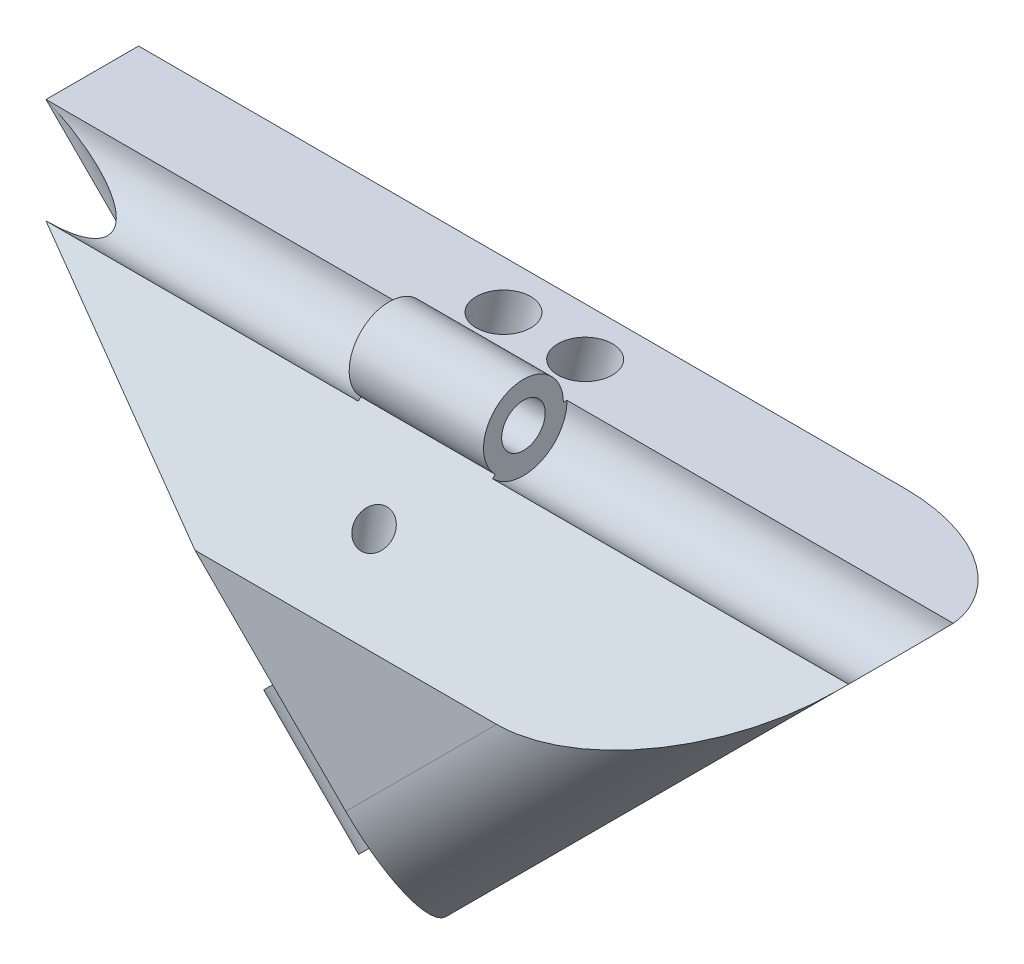
SolidWorks part; units mm, degrees
ref_plane "Front Plane" through (0, 0, 0) normal (1, 0, 0) x (0, 1, 0)
ref_plane "Top Plane" through (0, 0, 0) normal (0, 0, 1) x (0, 1, 0)
ref_plane "Right Plane" through (0, 0, 0) normal (0, 1, 0) x (-1, 0, 0)
sketch "Sketch1" plane through (0, 0, 0) normal (0, 0, 1) x (0, 1, 0)
  line L9 (8.3333, 25) -> (8.3333, -25)
  line L10 (-16.6667, 0) -> (8.3333, -25)
  line L11 (-16.6667, 0) -> (8.3333, 25)
  line L12 (-4.1667, 12.5) -> (8.3333, -25) construction
  line L13 (8.3333, 25) -> (-4.1667, -12.5) construction
  point P1 (0, 0)
  dimension "D1" = 50
  dimension "D2" = 90
extrude "Boss-Extrude1" add sketch "Sketch1" along normal blind 15
sketch "Sketch2" plane through (0, 0, 0) normal (1, 0, 0) x (0, 1, 0)
  line L0 (0.8333, 15) -> (8.3333, 7.5)
  line L1 (8.3333, 15) -> (8.3333, 0) construction
  line L2 (8.3333, 7.5) -> (8.3333, 15)
  line L3 (8.3333, 15) -> (0.8333, 15)
  line L4 (-16.6667, 15) -> (8.3333, 15) construction
  line L5 (8.3333, 5.1) -> (8.3333, 5.3)
  circle A0 centre (8.3333, 7.5) radius 1.2
  circle A1 centre (8.3333, 7.5) radius 2.4
  circle A2 centre (8.3333, 7.5) radius 2.2
  dimension "D2" = 2.4
  dimension "D3" = 0.2
  dimension "D4" = 1
  dimension "D1" = 7.5
extrude "Cut-Extrude1" cut sketch "Sketch2" against normal through all both and the other way through all contours A1 L2 L3 L0 | A2 L2 A1 L0 | L2 A2 L0 A0 | L0 A2 L2 A0 | L0 A0 L2 | L2 A0 L0 | A1 region at (0, 5.6669, 12.8113) region at (0, 7.4751, 9.572) region at (0, 7.6811, 9.0747) region at (0, 7.0873, 8.6581) region at (0, 8.035, 8.2203) region at (0, 8.376, 7.3971)
extrude "Boss-Extrude2" add sketch "Sketch2<5>" along normal blind 3.7 and the other way blind 3.7 contours A2 L0 A1 L5 | A2 L2 A0 L0 | L2 A2 L0 A0 region at (0, 6.6734, 9.0928) region at (0, 7.6811, 9.0747) region at (0, 7.0873, 8.6581)
sketch "Sketch2<5>" plane through (0, 0, 0) normal (1, 0, 0) x (0, 1, 0) same geometry as "Sketch2"
sketch "Sketch4" plane through (8.3333, -8.3333, 0) normal (0.7071, -0.7071, 0) x (0.7071, 0.7071, 0)
  line L0 (-11.7851, 7.5) -> (-4.2851, 15)
  line L1 (-11.7851, 15) -> (-11.7851, 0) construction
  line L2 (-11.7851, 15) -> (12.9636, 15) construction
  line L3 (-4.2851, 15) -> (-11.7851, 15)
  line L4 (-11.7851, 15) -> (-11.7851, 7.5)
  line L5 (-11.7851, 5.1) -> (-11.7851, 7.5)
  circle A0 centre (-11.7851, 7.5) radius 1.2
  circle A1 centre (-11.7851, 7.5) radius 2.2
  circle A2 centre (-11.7851, 7.5) radius 2.4
  line M6 (12.9636, 15) -> (-11.7851, 15)
  line M7 (-11.7851, 15) -> (-11.7851, 0)
  dimension "D1" = 2.4
  dimension "D2" = 1
  dimension "D3" = 0.2
extrude "Cut-Extrude2" cut sketch "Sketch4" against normal through all contours L0 A0 L4 | A0 L0 M7 | L5 A1 L0 A0 | L0 A1 L4 A0 | L0 A2 L4 A1 | A2 L0 M6 M7 | A2 region at (0.211, -16.4557, 8.2203) region at (0.4098, -16.2568, 7.2599) region at (0.4612, -16.2055, 9.0747) region at (0.896, -15.7706, 6.9751) region at (0.6069, -16.0598, 9.572) region at (1.8855, -14.7812, 12.8113)
extrude "Boss-Extrude3" add sketch "Sketch4<3>" against normal blind 7.4 from offset 3.8 contours A2 L0 A1 M7 | L5 A1 L0 A0 | L4 A1 L5 A0 | L0 A1 L4 A0 region at (0.4612, -16.2055, 9.0747) region at (0.896, -15.7706, 6.9751) region at (-0.8833, -17.55, 7.5) region at (1.1737, -15.4929, 9.0928) offset against normal yes
sketch "Sketch4<3>" plane through (8.3333, -8.3333, 0) normal (0.7071, -0.7071, 0) x (0.7071, 0.7071, 0) same geometry as "Sketch4"
ref_plane "Plane1" through (0, 0, 2.65) normal (0, 0, 1) x (0, 1, 0)
fillet "Fillet1" radius 5.5 1 edges at (12.5, -4.1667, 0)
fillet "Fillet2" radius 5.5 1 edges at (11.4017, -5.265, 15)
sketch "Sketch8" plane through (-6.8183, -6.8183, 9.6426) normal (-0.5, -0.5, 0.7071) x (0.866, -0.2887, 0.4082)
  line L0 (3.0196, -3.1517) -> (7.8731, 3.7122) construction
  line L1 (-0.0015, -1.0155) -> (6.0406, -5.2879) construction
  line L2 (-0.0867, 9.3407) -> (9.5061, 2.5575) construction
  circle A0 centre (5.4463, 0.2803) radius 1
  dimension "D1" = 2
sketch "Sketch10" plane through (0, 7.9167, 7.9167) normal (0, 0.7071, 0.7071) x (-1, 0, 0)
  line L0 (0, 1.6107) -> (0, 10.0173) construction
  line L1 (3.7, 1.6107) -> (-3.7, 1.6107) construction
  line L2 (-9.7218, 10.0173) -> (6.8934, 10.0173) construction
  circle A0 centre (0, 5.814) radius 1
  dimension "D1" = 2
loft "Cut-Loft1" cut profiles "Sketch10", "Sketch8" connector at (-0.78, 4.248, 11.5854) connector at (-2.943, -7.6876, 11.7682)
sketch "Sketch11" plane through (-8.3333, -8.3333, 0) normal (-0.7071, -0.7071, 0) x (0.7071, -0.7071, 0)
  line L0 (3.5351, 2.65) -> (5.0351, 2.65) construction
  line L1 (4.2851, 5.3) -> (4.2851, 0) construction
  line L2 (0.5851, 5.3) -> (7.9851, 5.3) construction
  line L3 (-23.5702, 0) -> (6.2851, 0) construction
  circle A0 centre (2.0351, 2.65) radius 1.5
  circle A1 centre (6.5351, 2.65) radius 1.5
  point P4 (3.5351, 2.65)
  point P5 (5.0351, 2.65)
  point P14 (4.2851, 2.65)
  dimension "D1" = 3
  dimension "D2" = 1.5
sketch "Sketch12" plane through (0, 8.3333, 0) normal (0, 1, 0) x (-1, 0, 0)
  line L0 (0, 5.3) -> (0, 0) construction
  line L1 (3.7, 5.3) -> (-3.7, 5.3) construction
  line L2 (-0.75, 2.65) -> (0.75, 2.65) construction
  circle A0 centre (-2.25, 2.65) radius 1.5
  circle A1 centre (2.25, 2.65) radius 1.5
  point P9 (0.75, 2.65)
  point P10 (-0.75, 2.65)
  point P11 (0, 2.65)
  point P14 (2.25, 2.65)
  dimension "D1" = 1.5
  dimension "D2" = 3
loft "Cut-Loft2" cut section "Sketch12" section "Sketch11" connector at (-1.9689, 8.3333, 1.1766) connector at (-7.8585, -8.8082, 2.025)
loft "Cut-Loft3" cut section "Sketch12<4>" section "Sketch11<3>" connector at (1.726, 8.3333, 1.2445) connector at (-3.9254, -12.7412, 1.1806)
sketch "Sketch12<4>" plane through (0, 8.3333, 0) normal (0, 1, 0) x (-1, 0, 0) same geometry as "Sketch12"
sketch "Sketch11<3>" plane through (-8.3333, -8.3333, 0) normal (-0.7071, -0.7071, 0) x (0.7071, -0.7071, 0) same geometry as "Sketch11"
